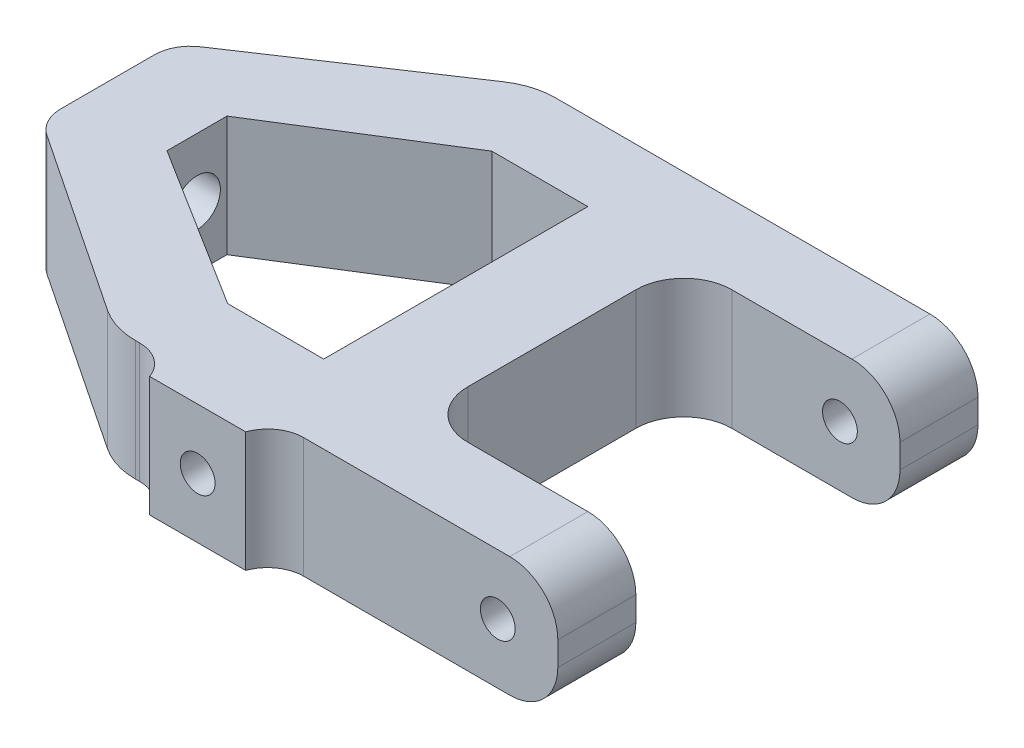
SolidWorks part; units mm, degrees
ref_plane "Front" through (0, 0, 0) normal (0, 0, 1) x (1, 0, 0)
ref_plane "Top" through (0, 0, 0) normal (0, 1, 0) x (1, 0, 0)
ref_plane "Right" through (0, 0, 0) normal (1, 0, 0) x (0, 0, -1)
sketch "Sketch1" plane through (0, 0, 0) normal (0, 1, 0) x (1, 0, 0)
  line L1 (0, 0) -> (55, 0)
  line L2 (0, 0) -> (0, -35)
  line L3 (0, -35) -> (55, -35)
  line L4 (55, 0) -> (55, -35)
  dimension "D1" = 35
  dimension "D2" = 55
extrude "Boss-Extrude1" add sketch "Sketch1" along normal blind 10
sketch "Sketch2" plane through (55, 0, 0) normal (1, 0, 0) x (0, 0, -1)
  line L0 (-35, 10) -> (0, 10) construction
  line L1 (-28.5, 10) -> (-6.5, 10)
  line L2 (-28.5, 10) -> (-28.5, 0)
  line L3 (-28.5, 0) -> (-6.5, 0)
  line L4 (-6.5, 10) -> (-6.5, 0)
  line L5 (-35, 0) -> (0, 0) construction
  line L6 (-35, 10) -> (-35, 0) construction
  line L7 (0, 10) -> (0, 0) construction
  dimension "D1" = 6.5
  dimension "D2" = 6.5
extrude "Cut-Extrude1" cut sketch "Sketch2" against normal blind 34
sketch "Sketch9" plane through (0, 0, 0) normal (0, -1, 0) x (-1, 0, 0)
  line L0 (0, -12) -> (-18, 0)
  line L1 (0, 0) -> (0, -35) construction
  line L2 (-55, 0) -> (0, 0) construction
  line L3 (-18, 0) -> (0, 0)
  line L4 (0, 0) -> (0, -12)
  line L5 (0, -23) -> (-18, -35)
  line L6 (0, -35) -> (-55, -35) construction
  line L7 (-18, -35) -> (0, -35)
  line L8 (0, -35) -> (0, -23)
  dimension "D1" = 12
  dimension "D2" = 12
  dimension "D3" = 18
  dimension "D4" = 18
extrude "Cut-Extrude6" cut sketch "Sketch9" against normal through all
sketch "Sketch10" plane through (0, 0, 0) normal (0, -1, 0) x (-1, 0, 0)
  line L0 (-21, -6.5) -> (-7.4446, -15)
  line L1 (-7.4446, -15) -> (-7.4446, -20)
  line L2 (-7.4446, -20) -> (-21, -28.5)
  line L3 (-21, -28.5) -> (-21, -6.5)
  dimension "D1" = 16
  dimension "D2" = 16
  dimension "D3" = 5
extrude "Cut-Extrude7" cut sketch "Sketch10" against normal through all
sketch "Sketch11" plane through (0, 0, 0) normal (0, -1, 0) x (-1, 0, 0)
  line L0 (-21, -6.5) -> (-55, -6.5) construction
  line L1 (-29, -28.5) -> (-37, -28.5)
  line L2 (-29, -28.5) -> (-29, -6.5)
  line L3 (-29, -6.5) -> (-37, -6.5)
  line L4 (-37, -28.5) -> (-37, -6.5)
  line L6 (-55, -35) -> (-55, -28.5) construction
  point P7 (0, 0)
  point P8 (0, 0)
  point P9 (0, 0)
  dimension "D1" = 8
  dimension "D2" = 18
extrude "Boss-Extrude3" add sketch "Sketch11" against normal blind 10
sketch "Sketch12" plane through (0, 0, 35) normal (0, 0, 1) x (1, 0, 0)
  line L0 (55, 10) -> (55, 0) construction
  line L2 (18, 0) -> (55, 0) construction
  circle A0 centre (50, 5) radius 1.45
  dimension "D1" = 2.9
  dimension "D2" = 5
  dimension "D3" = 5
extrude "Cut-Extrude8" cut sketch "Sketch12" against normal through all
sketch "Sketch13" plane through (0, 0, 0) normal (-1, 0, 0) x (0, 0, 1)
  circle A0 centre (17.5, 5) radius 1.95
  dimension "D1" = 3.9
extrude "Cut-Extrude9" cut sketch "Sketch13" against normal blind 11
fillet "Fillet4" radius 4 4 edges at (55, 10, 31.75) (55, 0, 31.75) (55, 10, 3.25) (55, 0, 3.25)
fillet "Fillet5" radius 3 2 edges at (0, 5, 12) (0, 5, 23)
fillet "Fillet6" radius 6 2 edges at (18, 5, 35) (18, 5, 0)
fillet "Fillet7" radius 4 2 edges at (37, 5, 28.5) (37, 5, 6.5)
sketch "Sketch14" plane through (0, 0, 35) normal (0, 0, 1) x (1, 0, 0)
  line L0 (19.8167, 10) -> (51, 10) construction
  line L1 (23, 10) -> (31, 10)
  line L2 (23, 10) -> (23, 0)
  line L3 (23, 0) -> (31, 0)
  line L4 (31, 10) -> (31, 0)
  line L5 (19.8167, 0) -> (51, 0) construction
  line L6 (55, 6) -> (55, 4) construction
  dimension "D1" = 8
  dimension "D2" = 24
extrude "Boss-Extrude4" add sketch "Sketch14" along normal blind 2
sketch "Sketch15" plane through (0, 0, 37) normal (0, 0, 1) x (1, 0, 0)
  line L0 (31, 10) -> (23, 10) construction
  line L2 (31, 0) -> (31, 10) construction
  circle A0 centre (27, 5) radius 1.45
  dimension "D1" = 2.9
  dimension "D2" = 5
  dimension "D3" = 4
extrude "Cut-Extrude10" cut sketch "Sketch15" against normal blind 12
fillet "Fillet8" radius 3 2 edges at (23, 5, 35) (31, 5, 35)
